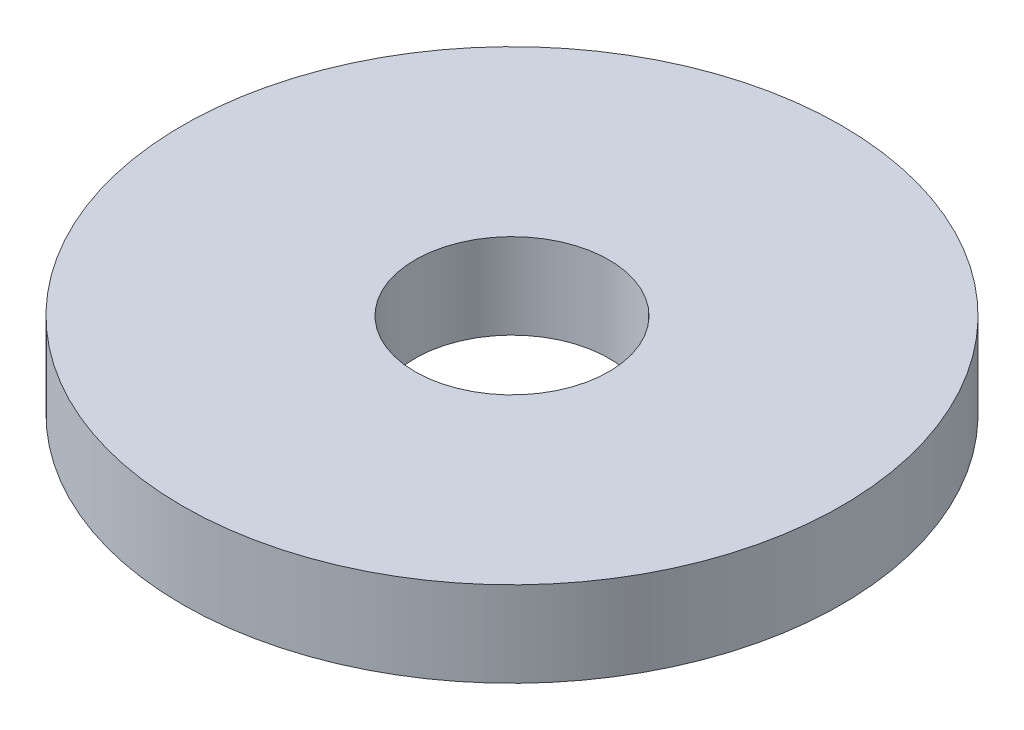
SolidWorks part; units mm, degrees
ref_plane "Front Plane" through (0, 0, 0) normal (0, 0, 1) x (1, 0, 0)
ref_plane "Top Plane" through (0, 0, 0) normal (0, 1, 0) x (1, 0, 0)
ref_plane "Right Plane" through (0, 0, 0) normal (1, 0, 0) x (0, 0, -1)
sketch "Sketch1" plane through (0, 0, 0) normal (0, 1, 0) x (1, 0, 0)
  circle A0 centre (0, 0) radius 85
  dimension "FLANGE_OD" = 170
extrude "Boss-Extrude1" add sketch "Sketch1" along normal blind 22
sketch "Sketch2" plane through (0, 0, 0) normal (0, 1, 0) x (1, 0, 0)
  circle A0 centre (0, 0) radius 25
  dimension "BORE_D" = 50
extrude "Cut-Extrude1" cut sketch "Sketch2" along normal through all
sketch "Sketch3" plane through (0, 22, 0) normal (0, 1, 0) x (1, 0, 0)
  circle A0 centre (0, 0) radius 18.3971 construction
  circle A1 centre (-18.3971, 0) radius 2.2641
  dimension "BOLT_D" = 4.5281
  dimension "BOLT_PCD" = 36.7943
extrude "Cut-Extrude2" cut sketch "Sketch3" against normal blind 15.0036 rebuild error yes
pattern_circular "CirPattern1" count 4 over 360 rebuild error yes
